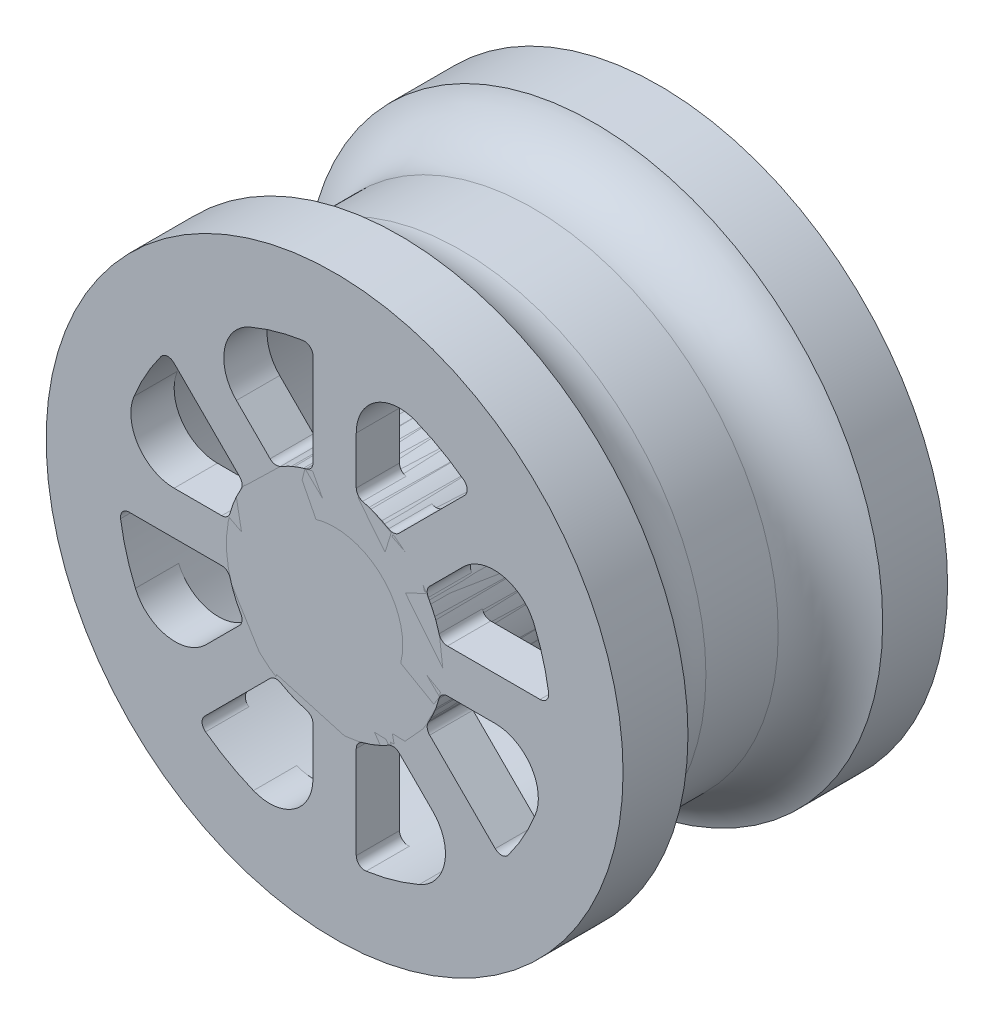
SolidWorks part; units mm, degrees
material "Alumina"
ref_plane "Front Plane" through (0, 0, 0) normal (0, 0, 1) x (1, 0, 0)
ref_plane "Top Plane" through (0, 0, 0) normal (0, 1, 0) x (1, 0, 0)
ref_plane "Right Plane" through (0, 0, 0) normal (1, 0, 0) x (0, 0, -1)
sketch "Sketch2" plane through (0, 0, 0) normal (1, 0, 0) x (0, 0, -1)
  line L2 (5.715, 16.9333) -> (9.525, 16.9333)
  line L3 (0, 0) -> (0, 203.2) construction
  line L6 (0, 0) -> (214.7812, 0) construction
  line L8 (-9.525, 12.7) -> (9.525, 12.7)
  line L9 (9.525, 12.7) -> (9.525, 16.9333)
  line L10 (-5.715, 16.9333) -> (-9.525, 16.9333)
  line L11 (0, 14.3933) -> (2.1229, 14.3933) construction
  line L13 (-9.525, 12.7) -> (-9.525, 16.9333)
  line L14 (2.1229, 14.3933) -> (-2.1229, 14.3933)
  line L15 (9.525, 14.3933) -> (27.5639, 14.3933) construction
  arc A3 (5.715, 16.9333) -> (2.1229, 14.3933) centre (2.1229, 18.2033) cw
  arc A4 (-5.715, 16.9333) -> (-2.1229, 14.3933) centre (-2.1229, 18.2033) ccw
  point P10 (0, 177.8)
  point P19 (0, 12.7)
  dimension "D5" = 3.81
  dimension "D6" = 2.54
  dimension "D1" = 16.9333
  dimension "D2" = 12.7
  dimension "D3" = 3.81
  dimension "D4" = 9.525
ref_plane "Plane1" through (0, 0, 50.8) normal (0, 0, 1) x (1, 0, 0)
revolve "Revolve1" add sketch "Sketch2" angle 360 about L6 region at (0, 16.7382, -7.62)
sketch "Sketch5" plane through (0, 0, 50.8) normal (0, 0, 1) x (1, 0, 0)
  circle A1 centre (0, 0) radius 6.35
  circle A2 centre (0, 0) radius 3.175 construction
  point P42 (0, 0)
  point P46 (0, 0)
  point P53 (0, 0)
  point P57 (0, 0)
  dimension "D1" = 12.7
  dimension "D5" = 6.35
extrude "Boss-Extrude3" add sketch "Sketch5" against normal blind 6.35 from surface separate body contours A1 region at (0, 0, 50.8) starting at face at (16.9333, 0, 9.525)
sketch "Sketch6" plane through (0, 0, 9.525) normal (0, 0, 1) x (1, 0, 0)
  circle A0 centre (0, 0) radius 4
  dimension "D1" = 8
extrude "Cut-Extrude4" cut sketch "Sketch6" against normal blind 25.4 from surface starting at face at (16.9333, 0, 9.525)
ref_axis "Axis1" through (0, 0, 3.175) along (0, 0, 1)
sketch "Sketch10" plane through (0, 0, 3.175) normal (0, 0, -1) x (-1, 0, 0)
  circle A0 centre (0, 0) radius 6.35
  circle A1 centre (0, 0) radius 16.9333 construction
  circle A2 centre (0, 0) radius 6.35 construction
extrude "Boss-Extrude7" add sketch "Sketch10" along normal blind 21.58 from surface separate body starting at face at (4, 0, 9.525)
sketch "Sketch11" plane through (0, 0, -12.055) normal (0, 0, -1) x (-1, 0, 0)
  line L0 (-1.524, -1.9685) -> (1.524, -1.9685)
  line L1 (-1.524, 1.9685) -> (1.524, 1.9685)
  line L2 (0, 6.35) -> (0, -6.35) construction
  line L3 (-3.4925, 0) -> (3.4925, 0) construction
  arc A0 (1.524, 1.9685) -> (1.524, -1.9685) centre (1.524, 0) cw
  circle A1 centre (0, 0) radius 6.35 construction
  arc A2 (-1.524, 1.9685) -> (-1.524, -1.9685) centre (-1.524, 0) ccw
  point P11 (0, -1.9685)
  point P13 (0, 1.9685)
  dimension "D1" = 1.524
  dimension "D2" = 3.937
extrude "Cut-Extrude5" cut sketch "Sketch11" against normal up to surface (15.23 mm away) up to face at (4, 0, 3.175)
sketch "Sketch12" plane through (0, 0, 50.8) normal (0, 0, 1) x (1, 0, 0)
  line L0 (0, 19.05) -> (0, -19.05) construction
  line L1 (1.27, 6.2217) -> (1.27, 12.6363)
  line L2 (-1.27, 6.2217) -> (-1.27, 12.6363)
  line L3 (5.2974, 3.5014) -> (9.8333, 8.0372)
  line L4 (3.5014, 5.2974) -> (8.0372, 9.8333)
  line L5 (6.2217, -1.27) -> (12.6363, -1.27)
  line L6 (6.2217, 1.27) -> (12.6363, 1.27)
  line L7 (3.5014, -5.2974) -> (8.0372, -9.8333)
  line L8 (5.2974, -3.5014) -> (9.8333, -8.0372)
  line L9 (-1.27, -6.2217) -> (-1.27, -12.6363)
  line L10 (1.27, -6.2217) -> (1.27, -12.6363)
  line L11 (-5.2974, -3.5014) -> (-9.8333, -8.0372)
  line L12 (-3.5014, -5.2974) -> (-8.0372, -9.8333)
  line L13 (-6.2217, 1.27) -> (-12.6363, 1.27)
  line L14 (-6.2217, -1.27) -> (-12.6363, -1.27)
  line L15 (-3.5014, 5.2974) -> (-8.0372, 9.8333)
  line L16 (-5.2974, 3.5014) -> (-9.8333, 8.0372)
  circle A0 centre (0, 0) radius 6.35
  arc A3 (-1.27, 12.6363) -> (1.27, 12.6363) centre (0, 0) cw
  arc A4 (8.0372, 9.8333) -> (9.8333, 8.0372) centre (0, 0) cw
  arc A5 (12.6363, 1.27) -> (12.6363, -1.27) centre (0, 0) cw
  arc A6 (9.8333, -8.0372) -> (8.0372, -9.8333) centre (0, 0) cw
  arc A7 (1.27, -12.6363) -> (-1.27, -12.6363) centre (0, 0) cw
  arc A8 (-8.0372, -9.8333) -> (-9.8333, -8.0372) centre (0, 0) cw
  arc A9 (-12.6363, -1.27) -> (-12.6363, 1.27) centre (0, 0) cw
  arc A10 (-9.8333, 8.0372) -> (-8.0372, 9.8333) centre (0, 0) cw
  circle A11 centre (0, 0) radius 12.7 construction
  point P45 (0, 0)
  dimension "D1" = 12.7
  dimension "D2" = 1.27
  dimension "D3" = 8
extrude "Boss-Extrude8" add sketch "Sketch12" against normal blind 2.54 from surface contours A3 L0 A0 L1 | L0 A3 L2 A0 | A4 L4 A0 L3 | A5 L6 A0 L5 | A6 L8 A0 L7 | A0 L0 A7 L10 | L0 A0 L9 A7 | A8 L12 A0 L11 | A9 L14 A0 L13 | A10 L16 A0 L15 region at (0.6361, 9.493, 50.8) region at (-0.6361, 9.493, 50.8) region at (0.6361, -9.493, 50.8) region at (-0.6361, -9.493, 50.8) region at (6.7126, 6.7126, 50.8) region at (-6.7126, 6.7126, 50.8) region at (-6.7126, -6.7126, 50.8) region at (6.7126, -6.7126, 50.8) region at (9.493, 0, 50.8) region at (-9.493, 0, 50.8) starting at face at (4, 0, 9.525)
fillet "Fillet1" radius 2.54 8 edges at (-8.0372, 9.8333, 8.255) (-12.6363, 1.27, 8.255) (-9.8333, -8.0372, 8.255) (-1.27, -12.6363, 8.255) (8.0372, -9.8333, 8.255) (12.6363, -1.27, 8.255) (9.8333, 8.0372, 8.255) (1.27, 12.6363, 8.255)
fillet "Fillet2" radius 0.508 24 edges at (8.0372, 9.8333, 8.255) (3.5014, 5.2974, 8.255) (1.27, 6.2217, 8.255) (-3.5014, 5.2974, 8.255) (-1.27, 6.2217, 8.255) (-1.27, 12.6363, 8.255) (-9.8333, 8.0372, 8.255) (-6.2217, 1.27, 8.255) (-5.2974, 3.5014, 8.255) (-6.2217, -1.27, 8.255) (-5.2974, -3.5014, 8.255) (-12.6363, -1.27, 8.255) (-8.0372, -9.8333, 8.255) (-1.27, -6.2217, 8.255) (-3.5014, -5.2974, 8.255) (1.27, -12.6363, 8.255) (1.27, -6.2217, 8.255) (3.5014, -5.2974, 8.255) (9.8333, -8.0372, 8.255) (5.2974, -3.5014, 8.255) (6.2217, -1.27, 8.255) (12.6363, 1.27, 8.255) (6.2217, 1.27, 8.255) (5.2974, 3.5014, 8.255)
other "Save Bodies1" [suppressed]
